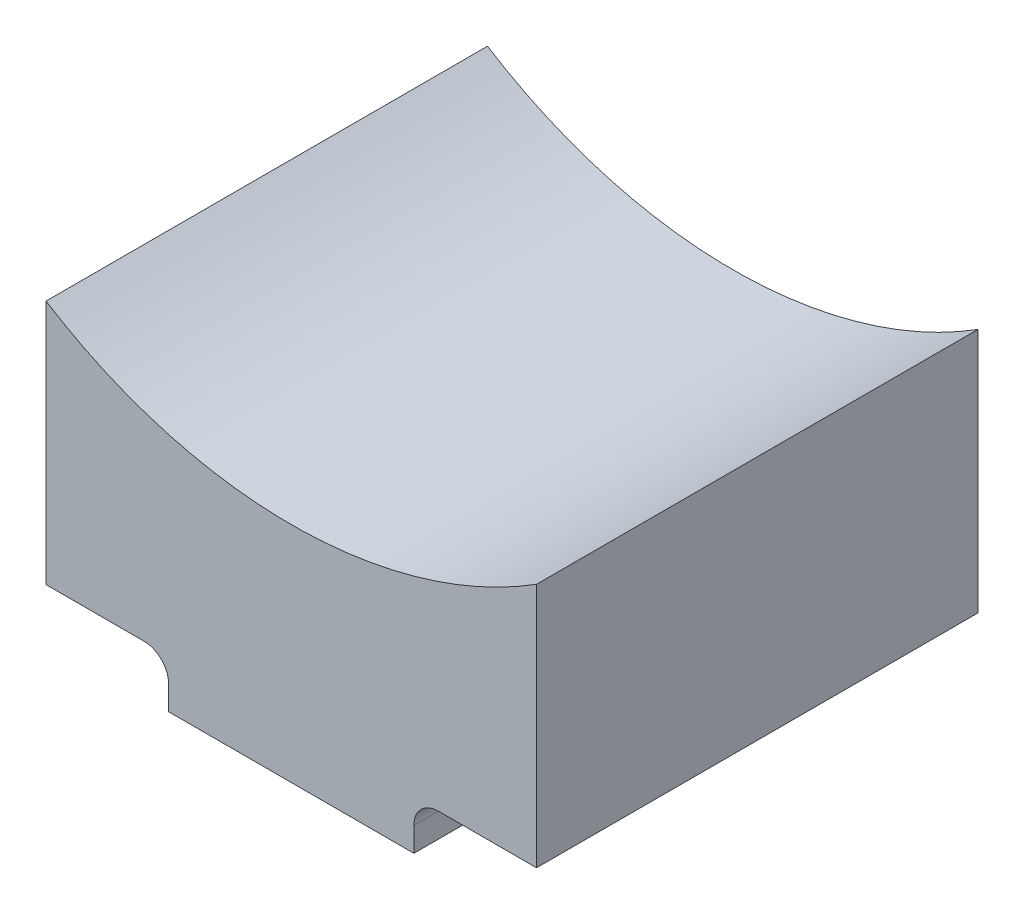
SolidWorks part; units mm, degrees
ref_plane "Front Plane" through (0, 0, 0) normal (0, 0, 1) x (1, 0, 0)
ref_plane "Top Plane" through (0, 0, 0) normal (0, 1, 0) x (1, 0, 0)
ref_plane "Right Plane" through (0, 0, 0) normal (1, 0, 0) x (0, 0, -1)
sketch "Sketch1" plane through (0, 0, 0) normal (0, 0, 1) x (1, 0, 0)
  line L0 (10, 3.9928) -> (10, -6.0185)
  line L1 (-10, 3.9928) -> (-10, -6.0185)
  line L2 (-10, -6.0185) -> (-6, -6.0185)
  line L3 (10, -6.0185) -> (6, -6.0185)
  line L4 (5, -7.0185) -> (5, -8.0072)
  line L5 (0, 0) -> (0, 15264.4079) construction
  line L6 (-5, -7.0185) -> (-5, -8.0072)
  line L11 (-5, -8.0072) -> (5, -8.0072)
  arc A0 (-10, 3.9928) -> (10, 3.9928) centre (0, 19.8337) ccw
  arc A1 (5, -7.0185) -> (6, -6.0185) centre (6, -7.0185) cw
  arc A2 (-5, -7.0185) -> (-6, -6.0185) centre (-6, -7.0185) ccw
  point P13 (5, -6.0185)
  point P17 (0, 0)
  dimension "D1" = 12
  dimension "D2" = 10
  dimension "D3" = 12
extrude "Boss-Extrude1" add sketch "Sketch1" along normal mid plane 18 contours A0 L0 L3 A1 L4 L11 L6 A2 L2 L1
